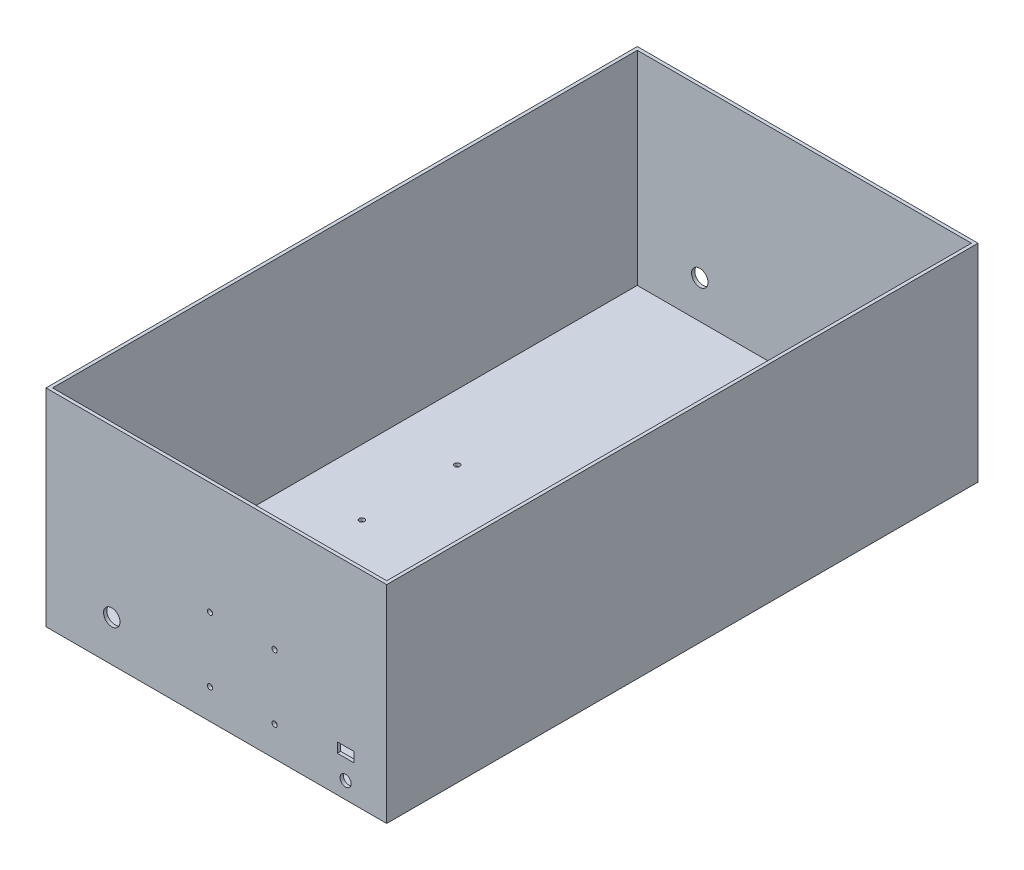
SolidWorks part; units mm, degrees
material "ABS"
ref_plane "Front Plane" through (0, 0, 0) normal (0, 0, 1) x (1, 0, 0)
ref_plane "Top Plane" through (0, 0, 0) normal (0, 1, 0) x (1, 0, 0)
ref_plane "Right Plane" through (0, 0, 0) normal (1, 0, 0) x (0, 0, -1)
sketch "Sketch2" plane through (0, 0, 0) normal (0, 1, 0) x (1, 0, 0)
  line L0 (-103.6, 179.8) -> (-103.6, -179.8)
  line L1 (-101.6, 177.8) -> (101.6, 177.8)
  line L2 (-101.6, 177.8) -> (-101.6, -177.8)
  line L3 (-101.6, -177.8) -> (101.6, -177.8)
  line L4 (101.6, 177.8) -> (101.6, -177.8)
  line L5 (-101.6, 177.8) -> (101.6, -177.8) construction
  line L6 (-101.6, -177.8) -> (101.6, 177.8) construction
  line L7 (-103.6, -179.8) -> (103.6, -179.8)
  line L8 (103.6, 179.8) -> (103.6, -179.8)
  line L9 (-103.6, 179.8) -> (103.6, 179.8)
  point P0 (0, 0)
  dimension "D1" = 355.6
  dimension "D2" = 203.2
  dimension "D3" = 2
extrude "Walls" add sketch "Sketch2" along normal blind 123.825
sketch "Sketch3" plane through (0, 0, 0) normal (0, -1, 0) x (1, 0, 0)
  line L1 (-103.6, -179.8) -> (103.6, -179.8)
  line L2 (-103.6, -179.8) -> (-103.6, 179.8)
  line L3 (-103.6, 179.8) -> (103.6, 179.8)
  line L4 (103.6, -179.8) -> (103.6, 179.8)
  line L5 (-103.6, -179.8) -> (103.6, 179.8) construction
  line L6 (-103.6, 179.8) -> (103.6, -179.8) construction
  point P0 (0, 0)
extrude "Base" add sketch "Sketch3" along normal blind 2
sketch "Sketch4" plane through (0, 0, -179.8) normal (0, 0, -1) x (-1, 0, 0)
  line L0 (103.6, -2) -> (-103.6, -2) construction
  line L3 (103.6, 123.825) -> (103.6, -2) construction
  line L4 (-83.6, 20) -> (-73.6, 20)
  line L5 (-83.6, 20) -> (-83.6, 26)
  line L6 (-83.6, 26) -> (-73.6, 26)
  line L7 (-73.6, 20) -> (-73.6, 26)
  line L8 (-83.6, 20) -> (-73.6, 26) construction
  line L9 (-83.6, 26) -> (-73.6, 20) construction
  line L10 (-103.6, 123.825) -> (-103.6, -2) construction
  circle A1 centre (63.6, 23) radius 5
  point P0 (-78.6, 23)
  dimension "D1" = 25
  dimension "D2" = 10
  dimension "D3" = 25
  dimension "D4" = 6
  dimension "D5" = 40
  dimension "D6" = 10
extrude "Cut-Extrude1" cut sketch "Sketch4" against normal through all
sketch "Sketch5" plane through (0, 0, -179.8) normal (0, 0, -1) x (-1, 0, 0)
  circle A0 centre (-78.6, 8.0963) radius 3.3782 construction
  circle A1 centre (-78.6, 8.0963) radius 3.3782
extrude "Cut-Extrude2" cut sketch "Sketch5" against normal through all
hole_wizard "1/4 Clearance Hole1" positions "Sketch7" profile "Sketch8" hole size "1/4" standard "ANSI Inch" end condition through all
sketch "Sketch7" plane through (0, -2, 0) normal (0, -1, 0) x (-1, 0, 0)
  line L0 (0, 0) -> (-103.6, 0) construction
  line L1 (-103.6, 179.8) -> (-103.6, -179.8) construction
  point P0 (-27, 0)
  point P2 (-5, 0)
  dimension "D1" = 27
  dimension "D2" = 22
sketch "Sketch8" plane through (27, -2, 0) normal (1, 0, 0) x (0, 0, -1)
  line L0 (0, 0) -> (0, 125.825)
  line L1 (0, 125.825) -> (3.3782, 125.825)
  line L2 (3.3782, 125.825) -> (3.3782, 0)
  line L5 (3.3782, 0) -> (0, 0)
  line L11 (0, -6.35) -> (0, 107.95) construction
  dimension "Thru Hole Dia." = 6.7564
  dimension "Thru Hole Depth" = 125.825
sketch "Sketch9" plane through (0, -2, 0) normal (0, -1, 0) x (1, 0, 0)
  circle A0 centre (92, 61.675) radius 1.6
  circle A1 centre (92, -61.675) radius 1.6
  circle A2 centre (49, 61.675) radius 1.6
  circle A3 centre (49, -61.675) radius 1.6
  circle A4 centre (27.1506, -126.7794) radius 1.6
  circle A5 centre (27.1506, -166.0794) radius 1.6
  circle A6 centre (-12.1494, -126.7794) radius 1.6
  circle A7 centre (-12.1494, -166.0794) radius 1.6
  circle A8 centre (23.9728, -62.9055) radius 1.6
  circle A9 centre (23.9728, -83.2055) radius 1.6
  circle A10 centre (3.6728, -62.9055) radius 1.6
  circle A11 centre (3.6728, -83.2055) radius 1.6
  circle A12 centre (-12.7908, 29.5071) radius 1.6
  circle A13 centre (-12.7908, -28.4929) radius 1.6
  circle A14 centre (-61.7908, -28.4929) radius 1.6
  circle A15 centre (-61.7908, 29.5071) radius 1.6
  circle A16 centre (-51.4971, 74.9976) radius 1.6
  circle A17 centre (-12.1971, 74.9976) radius 1.6
  circle A18 centre (-12.1971, 114.2976) radius 1.6
  circle A19 centre (-51.4971, 114.2976) radius 1.6
  dimension "D1" = 3.2
sketch "Sketch10" plane through (0, 0, 179.8) normal (0, 0, 1) x (1, 0, 0)
  circle A0 centre (-3.8836, 55.5451) radius 1.6
  circle A1 centre (35.4164, 55.5451) radius 1.6
  circle A2 centre (35.4164, 16.2451) radius 1.6
  circle A3 centre (-3.8836, 16.2451) radius 1.6
  dimension "D1" = 3.2
extrude "Cut-Extrude3" cut sketch "Sketch9" against normal up to next
extrude "Cut-Extrude4" cut sketch "Sketch10" against normal up to next
